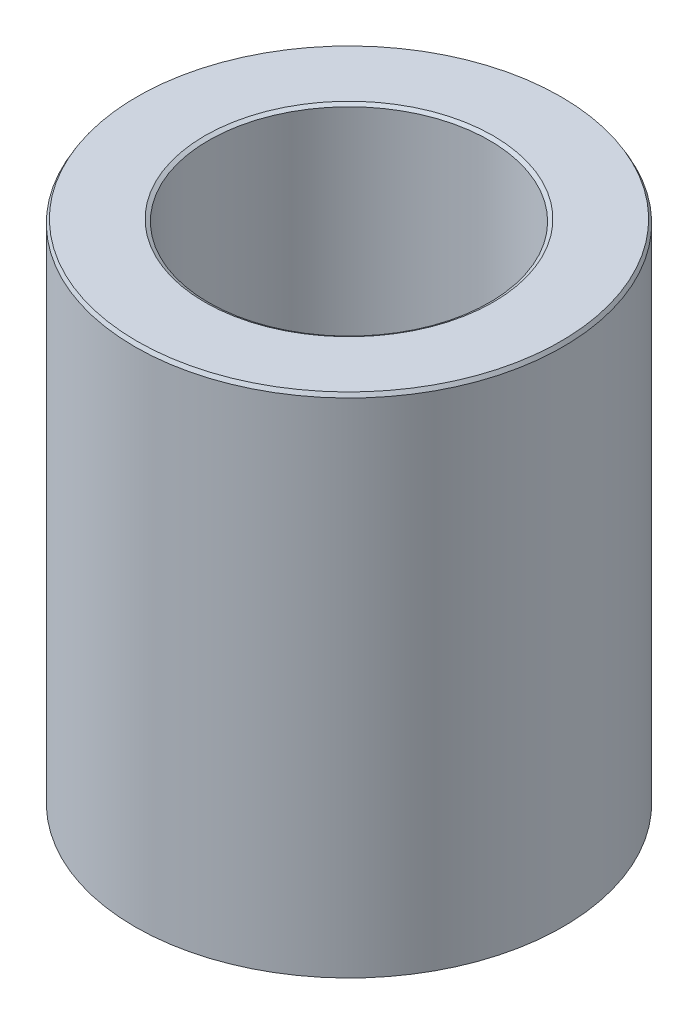
SolidWorks part; units mm, degrees
ref_plane "Front Plane" through (0, 0, 0) normal (0, 0, 1) x (1, 0, 0)
ref_plane "Top Plane" through (0, 0, 0) normal (0, 1, 0) x (1, 0, 0)
ref_plane "Right Plane" through (0, 0, 0) normal (1, 0, 0) x (0, 0, -1)
sketch "Sketch1" plane through (0, 0, 0) normal (0, 1, 0) x (1, 0, 0)
  circle A0 centre (0, 0) radius 55
  dimension "SLEEVE_OD" = 110
extrude "Boss-Extrude1" add sketch "Sketch1" along normal blind 130.5846
sketch "Sketch2" plane through (0, 0, 0) normal (0, 1, 0) x (1, 0, 0)
  circle A0 centre (0, 0) radius 36.0957
  dimension "BORE_D" = 72.1914
extrude "Cut-Extrude1" cut sketch "Sketch2" along normal through all
chamfer "Chamfer1" distance 0.9589 angle 30 4 edges at (0, 130.5846, 36.0957) (0, 0, 36.0957) (0, 0, 55) (0, 130.5846, 55) first distance on face at (0, 130.5846, 36.0957) first distance on face at (0, 0, 36.0957) first distance on face at (0, 130.5846, 55)
